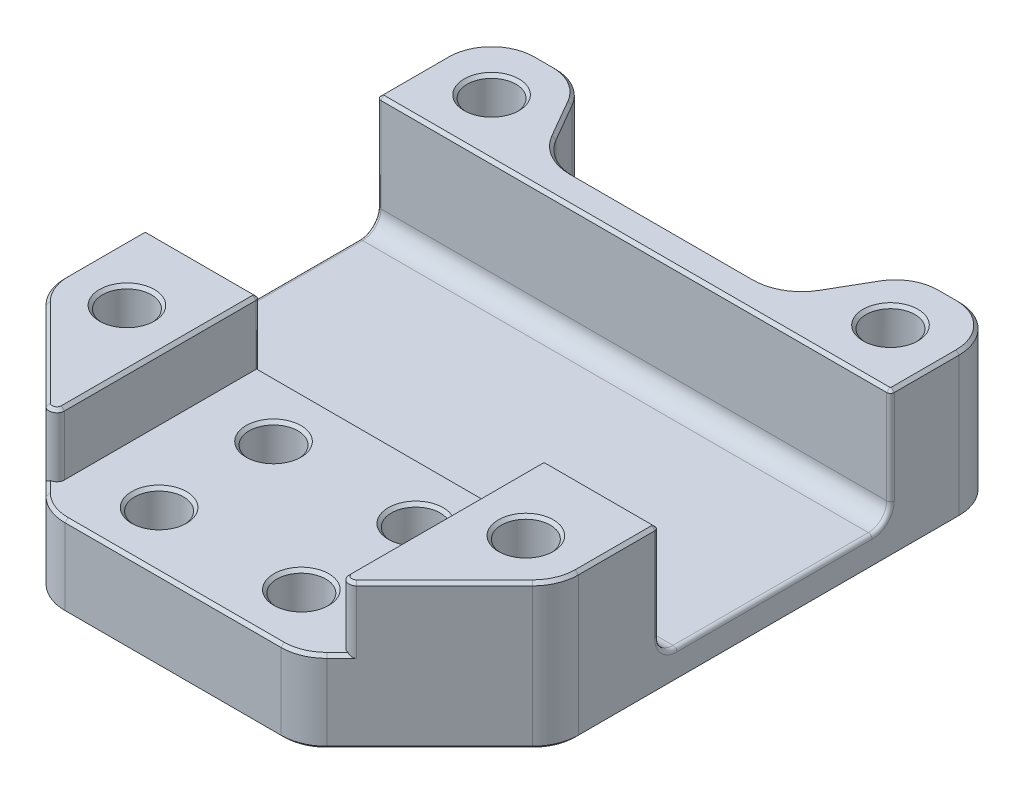
SolidWorks part; units mm, degrees
ref_plane "Front Plane" through (0, 0, 0) normal (1, 0, 0) x (0, 1, 0)
ref_plane "Top Plane" through (0, 0, 0) normal (0, 0, 1) x (0, 1, 0)
ref_plane "Right Plane" through (0, 0, 0) normal (0, 1, 0) x (-1, 0, 0)
sketch "Sketch1" plane through (0, 0, 0) normal (0, 0, 1) x (0, 1, 0)
  line L1 (-8.3312, -18.6436) -> (8.3312, -18.6436)
  line L2 (-8.3312, -18.6436) -> (-8.3312, 18.6436)
  line L3 (-8.3312, 18.6436) -> (8.3312, 18.6436)
  line L4 (8.3312, -18.6436) -> (8.3312, 18.6436)
  line L5 (-8.3312, -18.6436) -> (8.3312, 18.6436) construction
  line L6 (-8.3312, 18.6436) -> (8.3312, -18.6436) construction
  point P0 (0, 0)
  dimension "D1" = 16.6624
  dimension "D2" = 37.2872
extrude "Boss-Extrude1" add sketch "Sketch1" along normal mid plane 200
sketch "Sketch2" plane through (18.6436, 0, 0) normal (1, 0, 0) x (0, 1, 0)
  line L0 (-8.3312, -70.1) -> (-8.3312, -100.1)
  line L1 (-8.3312, -100.1) -> (-15.2, -100.1)
  line L2 (-15.2, -100.1) -> (-15.2, -130.5)
  line L3 (-15.2, -130.5) -> (-0.1, -130.5)
  line L4 (-8.3312, -100) -> (8.3312, -100)
  line L5 (8.3312, -100) -> (8.3312, 100)
  line L6 (8.3312, 100) -> (-8.3312, 100)
  line L7 (-8.3312, 100) -> (-8.3312, -100)
  line L8 (-8.3312, -100) -> (8.3312, -100)
  line L9 (8.3312, -100) -> (8.3312, 100)
  line L10 (8.3312, 100) -> (-8.3312, 100)
  line L11 (-8.3312, 100) -> (-8.3312, -100)
  line L12 (-0.1, -130.5) -> (-0.1, -145.5)
  line L13 (-0.1, -145.5) -> (-19.1, -145.5)
  line L14 (-19.1, -145.5) -> (-19.1, -70.1)
  line L15 (-19.1, -70.1) -> (-8.3312, -70.1)
  line L16 (0, -100) -> (0, -140.2396)
  line L17 (-0.1, -130.5) -> (-0.1, -70.1)
  line L18 (-0.1, -70.1) -> (-8.3312, -70.1)
  line L19 (-8.3312, -100.1) -> (0, -100.1)
  line M14 (-8.3312, -100) -> (8.3312, -100)
  line M17 (-8.3312, 100) -> (-8.3312, -100)
  dimension "D2" = 30.4
  dimension "D3" = 0.1
  dimension "D4" = 0.1
  dimension "D5" = 15.2
  dimension "D6" = 3.9
  dimension "D7" = 15
  dimension "D8" = 30
  dimension "D1" = 0
ref_plane "Plane1" through (0, 0, 0) normal (1, 0, 0) x (0, 0, -1)
extrude "Boss-Extrude2" add sketch "Sketch2" against normal up to surface (18.6436 mm away) separate body contours L15 L14 L13 L12 L3 L2 L1 L0 M17 region at (18.6436, -9.1088, -85.05) up to plane "Plane1"
extrude "Boss-Extrude3" add sketch "Sketch2<3>" along normal blind 15 contours L15 L14 L13 L12 L3 L2 L1 L0 M17 | L17 L18 M17 M14 | L0 L19 L17 M14 region at (18.6436, -4.2156, -85.05) region at (18.6436, -9.1088, -85.05) region at (18.6436, -4.2156, -100.05)
sketch "Sketch2<3>" plane through (18.6436, 0, 0) normal (1, 0, 0) x (0, 1, 0) same geometry as "Sketch2"
ref_plane "Plane2" through (0, 0, 0) normal (0, 1, 0) x (1, 0, 0)
delete or keep bodies "Body-Delete/Keep 1" type delete bodies bodies 101
sketch "Sketch3" plane through (0, -19.1, 0) normal (0, -1, 0) x (1, 0, 0)
  line L0 (0, -70.1) -> (33.6436, -70.1) construction
  line L1 (33.6436, -145.5) -> (33.6436, -70.1) construction
  line L2 (0, -70.1) -> (33.6436, -70.1)
  line L3 (33.6436, -145.5) -> (33.6436, -70.1)
  line L4 (0, -145.5) -> (33.6436, -145.5) construction
  line L5 (0, -145.5) -> (33.6436, -145.5)
  line L6 (0, -130.5) -> (33.6436, -130.5) construction
  line L7 (0, -130.5) -> (33.6436, -130.5)
  line L8 (18.6436, -70.1) -> (18.6436, -100.1) construction
  line L9 (0, -100.1) -> (33.6436, -100.1) construction
  line L10 (18.6436, -70.1) -> (18.6436, -100.1)
  line L11 (0, -100.1) -> (33.6436, -100.1)
  line L12 (9.3218, -77.6) -> (9.3218, -70.1) construction
  line L13 (0, -55) -> (0, 55) construction
  line L14 (26.1436, -90.2066) -> (26.1436, -70.1) construction
  line L15 (16.6436, -70.1) -> (33.6436, -87.1)
  line L16 (26.1436, -90.2066) -> (33.6436, -87.1) construction
  line L17 (26.1436, -138) -> (33.6436, -138) construction
  line L18 (0, -134.5) -> (15.4626, -134.5)
  line L19 (0, -70.1) -> (0, -145.5) construction
  line L20 (15.4626, -134.5) -> (21.8135, -145.5)
  line L21 (26.1436, -138) -> (21.8135, -145.5) construction
  circle A0 centre (9.3218, -92.6) radius 3.2
  circle A1 centre (9.3218, -92.6) radius 5.2 construction
  circle A2 centre (9.3218, -77.6) radius 3.2
  circle A3 centre (9.3218, -77.6) radius 5.2 construction
  circle A4 centre (26.1436, -90.2066) radius 3.2
  circle A5 centre (26.1436, -138) radius 3.2
  line M21 (33.6436, -70.1) -> (0, -70.1)
  line M22 (0, -70.1) -> (0, -145.5)
  line M23 (0, -145.5) -> (33.6436, -145.5)
  dimension "D1" = 6.4
  dimension "D2" = 10.4
  dimension "D3" = 18.6436
  dimension "D4" = 9.3218
  dimension "D5" = 30
  dimension "D6" = 7.5
  dimension "D7" = 7.5
  dimension "D8" = 15
  dimension "D9" = 7.5
  dimension "D10" = 2
  dimension "D11" = 45
  dimension "D12" = 67.5
  dimension "D13" = 15
  dimension "D14" = 7.5
  dimension "D15" = 120
  dimension "D16" = 4
  dimension "D17" = 60
extrude "Cut-Extrude1" cut sketch "Sketch3" against normal through all contours L20 L18 M22 M23 | A5 | A4 | L10 L15 L3 M21 | L2 L15 L10 | A2 | A0 region at (17.9769, -19.1, -70.7667) region at (28.1173, -19.1, -75.8368) region at (9.4092, -19.1, -140.3124) region at (9.3218, -19.1, -92.6) region at (9.3218, -19.1, -77.6) region at (26.1436, -19.1, -90.2066) region at (26.1436, -19.1, -138)
fillet "Fillet1" radius 6 5 edges at (16.6436, -13.7156, -70.1) (33.6436, -9.6, -145.5) (21.8135, -9.6, -145.5) (15.4626, -9.6, -134.5) (33.6436, -9.6, -87.1)
fillet "Fillet3" radius 2.4 2 edges at (16.8218, -15.2, -130.5) (16.8218, -15.2, -100.1)
fillet "Fillet2" radius 0.5 6 edges at (33.6436, -6.45, -130.5) (18.6436, -4.2156, -100.1) (33.6436, -6.45, -100.1) (33.6436, -14.4971, -129.7971) (33.6436, -15.2, -115.3) (33.6436, -14.4971, -100.8029)
fillet "Fillet4" radius 1 1 edges at (18.6436, -4.2156, -72.1)
chamfer "Chamfer1" distance 0.4 angle 45 40 edges at (9.3218, -8.3312, -95.8) (9.3218, -19.1, -95.8) (9.3218, -8.3312, -80.8) (9.3218, -19.1, -80.8) (26.1436, -19.1, -93.4066) (26.1436, -0.1, -93.4066) (26.1436, -19.1, -141.2) (26.1436, -0.1, -141.2) (9.5718, -8.3312, -100.1) (19.3758, -8.3312, -72.8322) (16.4544, -8.3312, -70.5567) (7.0792, -8.3312, -70.1) (5.9993, -0.1, -134.5) (14.9985, -0.1, -135.3038) (18.638, -0.1, -140) (22.2776, -0.1, -144.6962) (16.5718, -0.1, -130.5) (26.4606, -0.1, -145.5) (33.4972, -0.1, -130.6464) (31.8862, -0.1, -143.7426) (33.6436, -0.1, -135.25) (33.6436, -0.1, -94.5926) (33.4972, -0.1, -99.9536) (33.1869, -0.1, -87.2892) (26.1436, -0.1, -100.1) (26.1185, -0.1, -79.5749) (18.79, -0.1, -99.9536) (18.6436, -0.1, -87.0571) (5.9993, -19.1, -134.5) (14.9985, -19.1, -135.3038) (18.638, -19.1, -140) (7.0792, -19.1, -70.1) (22.2776, -19.1, -144.6962) (16.4544, -19.1, -70.5567) (26.4606, -19.1, -145.5) (25.1436, -19.1, -78.6) (31.8862, -19.1, -143.7426) (33.1869, -19.1, -87.2892) (33.6436, -19.1, -114.5426) (19.2609, -0.1, -73.5903)
mirror "Mirror1" about plane through (0, 0, 0) normal (1, 0, 0) of bodies 104
equation "\"D4@Sketch3\"=\"D3@Sketch3\"/2"
equation "\"D6@Sketch3\"=\"D5@Sketch3\"/4"
equation "\"D7@Sketch3\"=\"D6@Sketch3\""
equation "\"D9@Sketch3\"=\"D8@Sketch3\"/2"
equation "\"D12@Sketch3\"=(180deg-\"D11@Sketch3\")/2"
equation "\"D14@Sketch3\"=\"D13@Sketch3\"/2"
equation "\"D17@Sketch3\"=\"D15@Sketch3\"/2"
